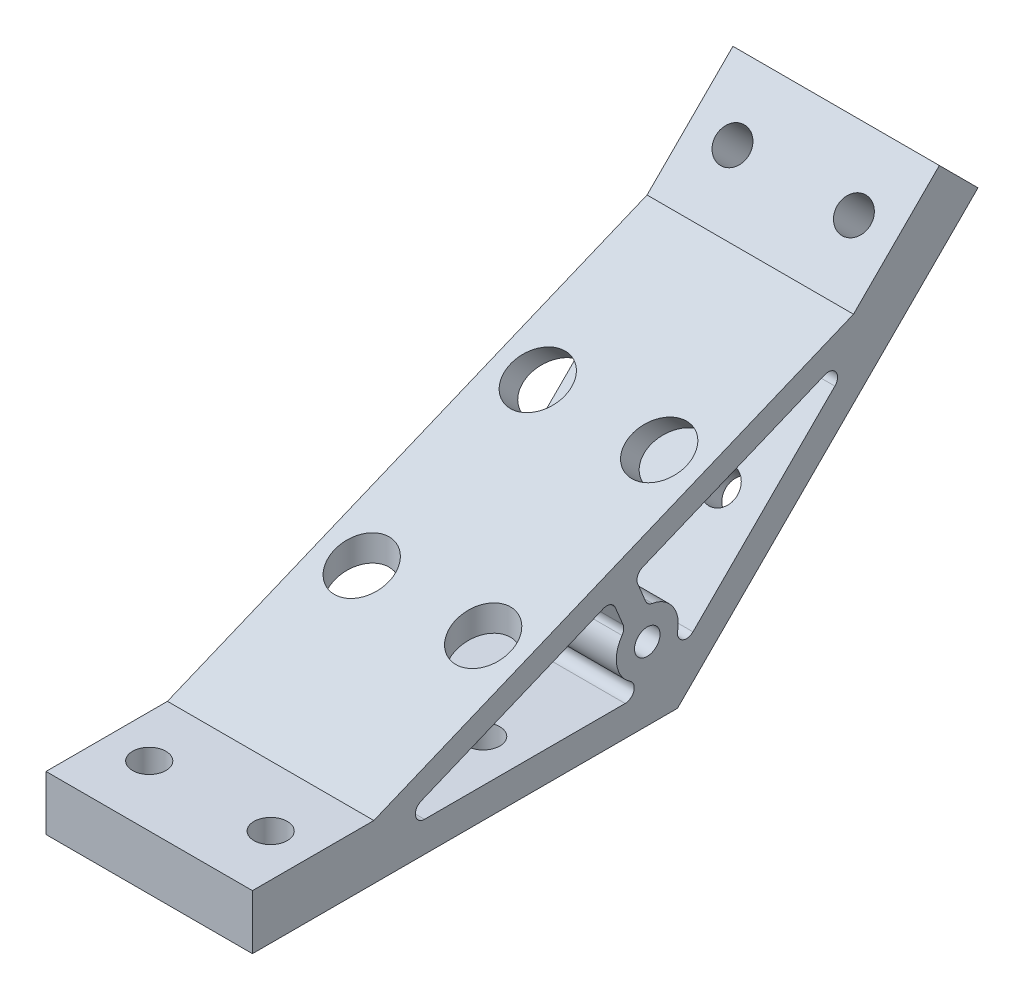
SolidWorks part; units mm, degrees
material "1060 Alloy"
ref_plane "Front Plane" through (0, 0, 0) normal (0, 0, 1) x (1, 0, 0)
ref_plane "Top Plane" through (0, 0, 0) normal (0, 1, 0) x (1, 0, 0)
ref_plane "Right Plane" through (0, 0, 0) normal (1, 0, 0) x (0, 0, -1)
ref_plane "Plane1" through (0, 0, 0) normal (1, 0, 0) x (0, 0, -1)
sketch "Sketch1" plane through (0, 0, 0) normal (1, 0, 0) x (0, 0, -1)
  line L0 (-70, 0) -> (0, 0)
  line L1 (0, 0) -> (49.4975, 49.4975)
  line L2 (49.4975, 49.4975) -> (43.1335, 55.8614)
  line L3 (43.1335, 55.8614) -> (28.9914, 41.7193)
  line L4 (28.9914, 41.7193) -> (-50, 9)
  line L5 (-50, 9) -> (-70, 9)
  line L6 (-70, 9) -> (-70, 0)
  line L7 (-6.5518, 21.0437) -> (-5.2641, 17.935)
  line L8 (2.5589, 9.63) -> (25.9249, 32.996)
  line L9 (24.2902, 35.4424) -> (-5.74, 23.0035)
  line L10 (-41.6633, 5) -> (-8.6189, 5)
  line L11 (-8.9596, 16.4042) -> (-10.2473, 19.5129)
  line L12 (-12.2072, 20.3247) -> (-42.2374, 7.8858)
  line L13 (0, 0) -> (-16.8353, 40.644) construction
  line L14 (0, 0) -> (0, -38.5069) construction
  arc A0 (-5.74, 23.0035) -> (-6.5518, 21.0437) centre (-5.166, 21.6177) ccw
  arc A1 (-5.2641, 17.935) -> (-4.1265, 17.0297) centre (-3.8783, 18.509) ccw
  arc A2 (-4.1265, 17.0297) -> (0.0281, 10.9882) centre (-4.9706, 12) cw
  arc A3 (0.0281, 10.9882) -> (2.5589, 9.63) centre (1.4983, 10.6906) ccw
  arc A4 (25.9249, 32.996) -> (24.2902, 35.4424) centre (24.8642, 34.0566) ccw
  circle A5 centre (-4.9706, 12) radius 2.1
  arc A6 (-42.2374, 7.8858) -> (-41.6633, 5) centre (-41.6633, 6.5) ccw
  arc A7 (-8.6189, 5) -> (-7.7897, 7.75) centre (-8.6189, 6.5) ccw
  arc A8 (-7.7897, 7.75) -> (-9.1239, 14.9597) centre (-4.9706, 12) cw
  arc A9 (-9.1239, 14.9597) -> (-8.9596, 16.4042) centre (-10.3455, 15.8302) ccw
  arc A10 (-10.2473, 19.5129) -> (-12.2072, 20.3247) centre (-11.6331, 18.9389) ccw
  dimension "D5" = 4.2
  dimension "D7" = 5.1
  dimension "D8" = 1.5
  dimension "D1" = 22.5
  dimension "D2" = 70
  dimension "D3" = 9
  dimension "D4" = 20
  dimension "D6" = 12
  dimension "D9" = 5
  dimension "D10" = 4
  dimension "D11" = 4
extrude "Boss-Extrude1" add sketch "Sketch1" against normal blind 17 and the other way blind 17
ref_plane "Plane2" through (0, 0, 0) normal (0, 1, 0) x (-1, 0, 0)
sketch "Sketch2" plane through (0, 0, 0) normal (0, 1, 0) x (-1, 0, 0)
  line L0 (10, 60) -> (10, 0) construction
  line L1 (10, 0) -> (-2.582, 0) construction
  circle A0 centre (10, 60) radius 2.75
  dimension "D3" = 5.5
  dimension "D1" = 10
  dimension "D2" = 60
extrude "Cut-Extrude1" cut sketch "Sketch2" along normal blind 9
ref_plane "Plane3" through (0, 0, 0) normal (0, 1, 0) x (-1, 0, 0)
sketch "Sketch3" plane through (0, 0, 0) normal (0, 1, 0) x (-1, 0, 0)
  line L0 (10, 60) -> (-10, 60) construction
  line L1 (0, 60) -> (0, 0) construction
  circle A0 centre (-10, 60) radius 2.75
  circle A1 centre (10, 60) radius 2.75 construction
extrude "Cut-Extrude2" cut sketch "Sketch3" along normal blind 9
ref_plane "Plane4" through (10, 0, 0) normal (1, 0, 0) x (0, 0, -1)
sketch "Sketch4" plane through (10, 0, 0) normal (1, 0, 0) x (0, 0, -1)
  line L0 (-25, 30) -> (-20.5, 30)
  line L1 (-20.5, 30) -> (-20.5, 9)
  line L2 (-20.5, 9) -> (-22.25, 9)
  line L3 (-22.25, 9) -> (-22.25, 0)
  line L4 (-22.25, 0) -> (-25, 0)
  line L5 (-25, 0) -> (-25, 30)
  line L6 (-25, 0) -> (-25, 30) construction
  line L7 (0, 0) -> (-22.25, 0) construction
  line L8 (-25, 0) -> (-25, -13.9852) construction
  dimension "D1" = 25
  dimension "D2" = 5.5
  dimension "D3" = 9
  dimension "D4" = 9
  dimension "D5" = 30
revolve "Cut-Revolve1" cut sketch "Sketch4" angle 360 about L6 reverse direction yes
ref_plane "Plane5" through (10, 0, 0) normal (1, 0, 0) x (0, 0, -1)
sketch "Sketch5" plane through (10, 0, 0) normal (1, 0, 0) x (0, 0, -1)
  line L0 (17.6777, 17.6777) -> (15.7331, 15.7331)
  line L1 (15.7331, 15.7331) -> (9.3692, 22.0971)
  line L2 (9.3692, 22.0971) -> (8.1317, 20.8597)
  line L3 (8.1317, 20.8597) -> (-6.7175, 35.7089)
  line L4 (-6.7175, 35.7089) -> (-3.5355, 38.8909)
  line L5 (-3.5355, 38.8909) -> (17.6777, 17.6777)
  line L6 (-3.5355, 38.8909) -> (17.6777, 17.6777) construction
  line L7 (0, 0) -> (15.7331, 15.7331) construction
  line L8 (0, 0) -> (49.4975, 49.4975) construction
  line L9 (17.6777, 17.6777) -> (30.6225, 4.7328) construction
  dimension "D1" = 25
  dimension "D2" = 5.5
  dimension "D3" = 9
  dimension "D4" = 9
  dimension "D5" = 30
revolve "Cut-Revolve2" cut sketch "Sketch5" angle 360 about L6 reverse direction yes
ref_plane "Plane6" through (-10, 0, 0) normal (1, 0, 0) x (0, 0, -1)
sketch "Sketch6" plane through (-10, 0, 0) normal (1, 0, 0) x (0, 0, -1)
  line L0 (-25, 30) -> (-20.5, 30)
  line L1 (-20.5, 30) -> (-20.5, 9)
  line L2 (-20.5, 9) -> (-22.25, 9)
  line L3 (-22.25, 9) -> (-22.25, 0)
  line L4 (-22.25, 0) -> (-25, 0)
  line L5 (-25, 0) -> (-25, 30)
  line L6 (-25, 0) -> (-25, 30) construction
revolve "Cut-Revolve3" cut sketch "Sketch6" angle 360 about L6 reverse direction yes
ref_plane "Plane7" through (-10, 0, 0) normal (1, 0, 0) x (0, 0, -1)
sketch "Sketch7" plane through (-10, 0, 0) normal (1, 0, 0) x (0, 0, -1)
  line L0 (17.6777, 17.6777) -> (15.7331, 15.7331)
  line L1 (15.7331, 15.7331) -> (9.3692, 22.0971)
  line L2 (9.3692, 22.0971) -> (8.1317, 20.8597)
  line L3 (8.1317, 20.8597) -> (-6.7175, 35.7089)
  line L4 (-6.7175, 35.7089) -> (-3.5355, 38.8909)
  line L5 (-3.5355, 38.8909) -> (17.6777, 17.6777)
  line L6 (-3.5355, 38.8909) -> (17.6777, 17.6777) construction
  line L7 (15.7331, 15.7331) -> (0, 0) construction
  line L8 (0, 0) -> (49.4975, 49.4975) construction
  line L9 (17.6777, 17.6777) -> (32.2951, 3.0602) construction
  dimension "D1" = 25
  dimension "D2" = 9
  dimension "D3" = 5.5
  dimension "D4" = 9
  dimension "D5" = 30
revolve "Cut-Revolve4" cut sketch "Sketch7" angle 360 about L6 reverse direction yes
ref_plane "Plane8" through (10, 0, 0) normal (1, 0, 0) x (0, 0, -1)
sketch "Sketch8" plane through (10, 0, 0) normal (1, 0, 0) x (0, 0, -1)
  line L0 (36.0624, 48.7904) -> (38.007, 50.7349)
  line L1 (38.007, 50.7349) -> (44.371, 44.371)
  line L2 (44.371, 44.371) -> (42.4264, 42.4264)
  line L3 (42.4264, 42.4264) -> (36.0624, 48.7904)
  line L4 (42.4264, 42.4264) -> (36.0624, 48.7904) construction
  line L5 (42.4264, 42.4264) -> (0, 0) construction
  line L6 (0, 0) -> (49.4975, 49.4975) construction
  line L7 (42.4264, 42.4264) -> (46.6114, 38.2414) construction
  line L8 (43.1335, 55.8614) -> (28.9914, 41.7193) construction
  dimension "D1" = 60
  dimension "D2" = 5.5
revolve "Cut-Revolve5" cut sketch "Sketch8" angle 360 about L4 reverse direction yes
ref_plane "Plane9" through (-10, 0, 0) normal (1, 0, 0) x (0, 0, -1)
sketch "Sketch9" plane through (-10, 0, 0) normal (1, 0, 0) x (0, 0, -1)
  line L0 (36.0624, 48.7904) -> (38.007, 50.7349)
  line L1 (38.007, 50.7349) -> (44.371, 44.371)
  line L2 (44.371, 44.371) -> (42.4264, 42.4264)
  line L3 (42.4264, 42.4264) -> (36.0624, 48.7904)
  line L4 (42.4264, 42.4264) -> (36.0624, 48.7904) construction
  line L5 (42.4264, 42.4264) -> (0, 0) construction
  line L6 (0, 0) -> (49.4975, 49.4975) construction
  line L7 (42.4264, 42.4264) -> (48.6512, 36.2016) construction
  line L8 (43.1335, 55.8614) -> (28.9914, 41.7193) construction
  dimension "D1" = 60
  dimension "D2" = 5.5
revolve "Cut-Revolve6" cut sketch "Sketch9" angle 360 about L4 reverse direction yes
